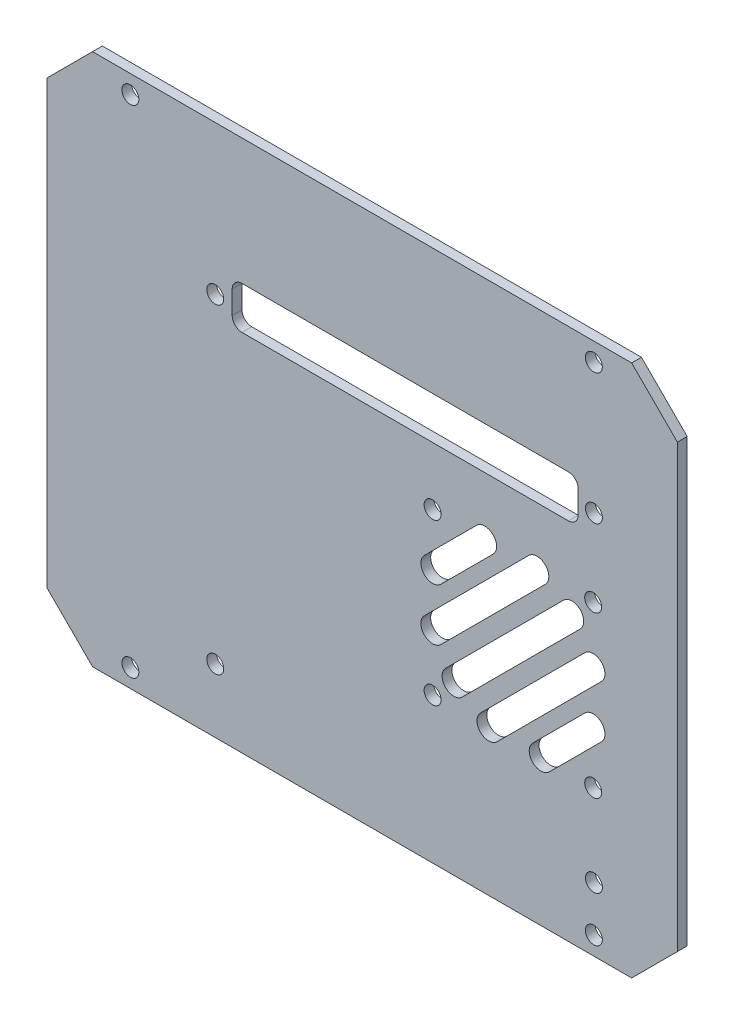
SolidWorks part; units mm, degrees
ref_plane "前视基准面" through (0, 0, 0) normal (0, 0, 1) x (1, 0, 0)
ref_plane "上视基准面" through (0, 0, 0) normal (0, 1, 0) x (1, 0, 0)
ref_plane "右视基准面" through (0, 0, 0) normal (1, 0, 0) x (0, 0, -1)
sketch "草图2" plane through (0, 0, -39.19) normal (0, 0, -1) x (-1, 0, 0)
  line L32 (-47.3467, -34.0538) -> (-40.3426, -41.058)
  line L33 (-40.3426, -41.058) -> (42.2491, -41.058)
  line L34 (42.2491, -41.058) -> (49.2533, -34.0538)
  line L35 (49.2533, -34.0538) -> (49.2533, 33.5378)
  line L36 (49.2533, 33.5378) -> (42.2491, 40.542)
  line L37 (-47.3467, 33.5378) -> (-47.3467, -34.0538)
  line L38 (-40.3426, 40.542) -> (-47.3467, 33.5378)
  line L39 (42.2491, 40.542) -> (-40.3426, 40.542)
  line L40 (-47.3467, -34.0538) -> (-40.3426, -41.058)
  line L41 (-40.3426, -41.058) -> (42.2491, -41.058)
  line L42 (42.2491, -41.058) -> (49.2533, -34.0538)
  line L43 (49.2533, -34.0538) -> (49.2533, 33.5378)
  line L44 (49.2533, 33.5378) -> (42.2491, 40.542)
  line L45 (-47.3467, 33.5378) -> (-47.3467, -34.0538)
  line L46 (-40.3426, 40.542) -> (-47.3467, 33.5378)
  line L47 (42.2491, 40.542) -> (-40.3426, 40.542)
  dimension "D1" = 0.2
extrude "凸台-拉伸1" add sketch "草图2" along normal blind 1.5
sketch "草图3" plane through (0, 0, -40.69) normal (0, 0, -1) x (-1, 0, 0)
  circle A0 centre (-34.5467, -38.258) radius 1.3
  circle A1 centre (36.4533, -38.258) radius 1.3
  circle A2 centre (-34.5467, 37.742) radius 1.3
  circle A3 centre (36.4533, 37.742) radius 1.3
  dimension "D1" = 2.6
extrude "切除-拉伸1" cut sketch "草图3" against normal through all
sketch "草图4" plane through (0, 0, -40.69) normal (0, 0, -1) x (-1, 0, 0)
  circle A1 centre (23.4533, -31.2932) radius 1.3
  circle A2 centre (23.4533, -31.2932) radius 1.3
  circle A3 centre (-34.5583, -31.2932) radius 1.3
  circle A4 centre (-34.5583, -31.2932) radius 1.3
  circle A5 centre (23.4533, 17.742) radius 1.3
  circle A6 centre (23.4533, 17.742) radius 1.3
  circle A7 centre (-34.5583, 17.742) radius 1.3
  circle A8 centre (-34.5583, 17.742) radius 1.3
  dimension "D1" = 0
  dimension "D2" = 0
  dimension "D3" = 0
  dimension "D4" = 0
extrude "切除-拉伸2" cut sketch "草图4" against normal up to next
sketch "草图5" plane through (0, 0, -40.69) normal (0, 0, -1) x (-1, 0, 0)
  line L1 (-32.1467, 14.742) -> (20.8533, 14.742)
  line L2 (-32.1467, 14.742) -> (-32.1467, 21.242)
  line L3 (-32.1467, 21.242) -> (20.8533, 21.242)
  line L4 (20.8533, 14.742) -> (20.8533, 21.242)
  line L7 (-47.3467, 33.5378) -> (-47.3467, -34.0538) construction
  line L9 (42.2491, 40.542) -> (-40.3426, 40.542) construction
  dimension "D1" = 53
  dimension "D2" = 6.5
  dimension "D3" = 15.2
  dimension "D4" = 19.3
extrude "切除-拉伸3" cut sketch "草图5" against normal up to next
fillet "圆角1" radius 1.5 4 edges at (32.1467, 21.242, -39.94) (32.1467, 14.742, -39.94) (-20.8533, 14.742, -39.94) (-20.8533, 21.242, -39.94)
sketch "草图7" plane through (0, 0, -40.69) normal (0, 0, -1) x (-1, 0, 0)
  circle A0 centre (-34.4467, 5.842) radius 1.3
  circle A1 centre (-34.4467, -18.758) radius 1.3
  circle A2 centre (-9.8467, 5.842) radius 1.3
  circle A3 centre (-9.8467, -18.758) radius 1.3
  circle A4 centre (-34.5583, 17.742) radius 1.3 construction
extrude "切除-拉伸4" cut sketch "草图7" against normal up to next
sketch "草图8" plane through (0, 0, -40.69) normal (0, 0, -1) x (-1, 0, 0)
  line L0 (-34.4467, 5.842) -> (-9.8467, -18.758) construction
  line L1 (-34.4467, 5.842) -> (-9.8467, 5.842) construction
  line L2 (-34.4467, 5.842) -> (-34.4467, -18.758) construction
  line L3 (-34.4467, -18.758) -> (-9.8467, -18.758) construction
  line L4 (-9.8467, 5.842) -> (-9.8467, -18.758) construction
  line L5 (-31.194, 2.5893) -> (-13.0994, -15.5053) construction
  line L6 (-29.9212, 3.8621) -> (-11.8266, -14.2325)
  line L7 (-32.4668, 1.3165) -> (-14.3722, -16.7781)
  line L8 (-34.4467, -2.758) -> (-18.4467, -18.758) construction
  line L9 (-33.1739, -1.4852) -> (-17.1739, -17.4852)
  line L10 (-35.7195, -4.0308) -> (-19.7195, -20.0308)
  line L11 (-25.8467, 5.842) -> (-9.8467, -10.158) construction
  line L12 (-24.5739, 7.1148) -> (-8.5739, -8.8852)
  line L13 (-27.1195, 4.5692) -> (-11.1195, -11.4308)
  line L14 (-17.8467, 5.842) -> (-9.8467, -2.158) construction
  line L15 (-16.5739, 7.1148) -> (-8.5739, -0.8852)
  line L16 (-19.1195, 4.5692) -> (-11.1195, -3.4308)
  line L17 (-34.4467, -10.758) -> (-26.4467, -18.758) construction
  line L18 (-33.1739, -9.4852) -> (-25.1739, -17.4852)
  line L19 (-35.7195, -12.0308) -> (-27.7195, -20.0308)
  arc A1 (-29.9212, 3.8621) -> (-32.4668, 1.3165) centre (-31.194, 2.5893) ccw
  arc A2 (-14.3722, -16.7781) -> (-11.8266, -14.2325) centre (-13.0994, -15.5053) ccw
  arc A3 (-33.1739, -1.4852) -> (-35.7195, -4.0308) centre (-34.4467, -2.758) ccw
  arc A4 (-19.7195, -20.0308) -> (-17.1739, -17.4852) centre (-18.4467, -18.758) ccw
  arc A5 (-24.5739, 7.1148) -> (-27.1195, 4.5692) centre (-25.8467, 5.842) ccw
  arc A6 (-11.1195, -11.4308) -> (-8.5739, -8.8852) centre (-9.8467, -10.158) ccw
  arc A7 (-16.5739, 7.1148) -> (-19.1195, 4.5692) centre (-17.8467, 5.842) ccw
  arc A8 (-11.1195, -3.4308) -> (-8.5739, -0.8852) centre (-9.8467, -2.158) ccw
  arc A9 (-33.1739, -9.4852) -> (-35.7195, -12.0308) centre (-34.4467, -10.758) ccw
  arc A10 (-27.7195, -20.0308) -> (-25.1739, -17.4852) centre (-26.4467, -18.758) ccw
  point P8 (-31.0608, 2.4561)
  point P9 (-34.4467, -3.1817)
  point P10 (-22.1467, -6.458)
  point P15 (-26.4467, -10.758)
  point P22 (-17.8467, -2.158)
  point P29 (-13.8467, 1.842)
  point P36 (-30.4467, -14.758)
  point P43 (-29.167, -18.758)
  point P44 (0, 0)
  point P45 (-29.167, -18.758)
  point P46 (-34.4467, -13.4782)
  point P47 (-34.4467, -10.9326)
  point P48 (-34.4467, -3.1817)
  point P49 (-32.0462, 3.4415)
  point P50 (0, 0)
  point P51 (-13.1411, -15.4636)
  point P52 (-18.1724, -18.758)
  point P53 (-26.3096, 5.842)
  point P54 (-18.0782, 5.842)
  dimension "D1" = 1.8
  dimension "D2" = 1.8
  dimension "D3" = 1.8
  dimension "D4" = 1.8
  dimension "D5" = 1.8
  dimension "D6" = 8
  dimension "D7" = 8
  dimension "D8" = 8
  dimension "D9" = 8
  dimension "D10" = 4.6
  dimension "D11" = 4.6
extrude "切除-拉伸5" cut sketch "草图8" against normal up to next
